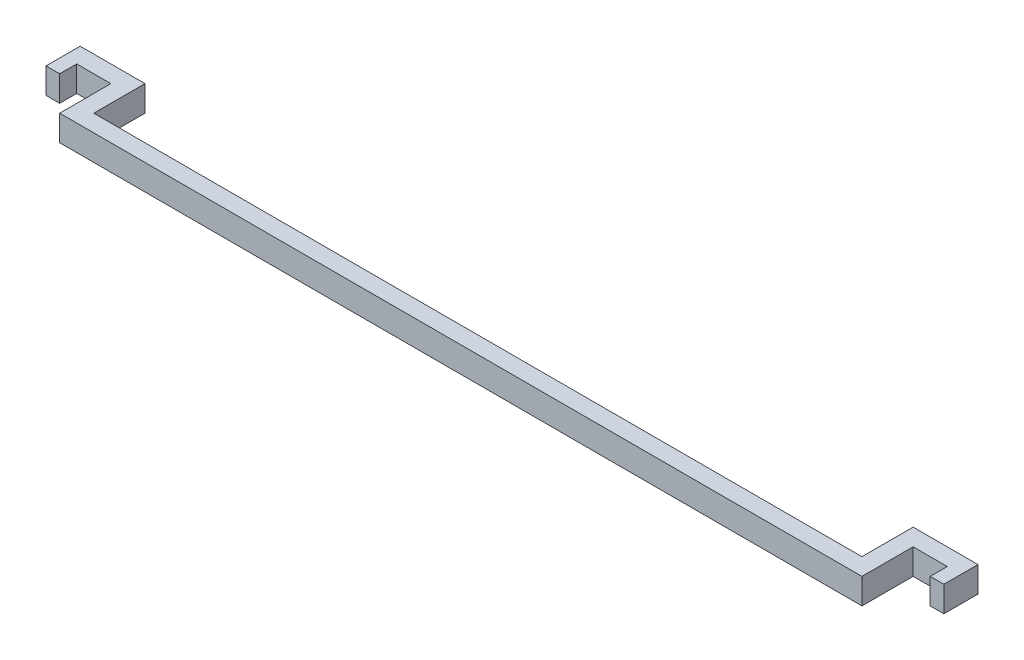
SolidWorks part; units mm, degrees
ref_plane "前视基准面" through (0, 0, 0) normal (0, 0, 1) x (1, 0, 0)
ref_plane "上视基准面" through (0, 0, 0) normal (0, 1, 0) x (1, 0, 0)
ref_plane "右视基准面" through (0, 0, 0) normal (1, 0, 0) x (0, 0, -1)
sketch "草图1" plane through (0, 0, 0) normal (0, 0, 1) x (1, 0, 0)
  line L1 (0, 0) -> (510, 0)
  line L2 (0, 0) -> (0, 15)
  line L3 (0, 15) -> (510, 15)
  line L4 (510, 0) -> (510, 15)
  dimension "D1" = 510
  dimension "D2" = 15
extrude "凸台-拉伸1" add sketch "草图1" along normal blind 10
sketch "草图2" plane through (0, 0, 10) normal (0, 0, 1) x (1, 0, 0)
  line L1 (510, 15) -> (518, 15)
  line L2 (510, 15) -> (510, 0)
  line L3 (510, 0) -> (518, 0)
  line L4 (518, 15) -> (518, 0)
  line L5 (0, 15) -> (-8, 15)
  line L6 (0, 15) -> (0, 0)
  line L7 (0, 0) -> (-8, 0)
  line L8 (-8, 15) -> (-8, 0)
  dimension "D1" = 8
  dimension "D2" = 8
extrude "凸台-拉伸2" add sketch "草图2" along normal blind 10 and the other way blind 10
sketch "草图3" plane through (0, 0, 0) normal (0, -1, 0) x (1, 0, 0)
  line L0 (0, 10) -> (510, 10) construction
  line L1 (20, 10) -> (30, 10)
  line L4 (30, 10) -> (30, 30)
  line L7 (30, 30) -> (480, 30)
  line L11 (490, 10) -> (480, 10)
  line L12 (480, 30) -> (480, 10)
  line L14 (490, 40) -> (490, 10)
  line L15 (510, 10) -> (510, 20) construction
  line L16 (0, 10) -> (0, 20) construction
  line L17 (490, 40) -> (20, 40)
  line L18 (20, 40) -> (20, 10)
  line M17 (510, 10) -> (0, 10)
  dimension "D1" = 10
  dimension "D2" = 10
  dimension "D3" = 20
  dimension "D4" = 10
  dimension "D5" = 20
  dimension "D6" = 30
extrude "凸台-拉伸3" add sketch "草图3" against normal up to surface (15 mm away) contours L7 L12 L4 M17 region at (255, 0, 33.8235) up to face at (255, 15, 12.5)
sketch "草图4" plane through (0, 0, 0) normal (0, -1, 0) x (1, 0, 0)
  line L0 (-8, 0) -> (518, 0) construction
  line L1 (30, 10) -> (480, 10)
  line L2 (30, 10) -> (30, 0)
  line L3 (30, 0) -> (480, 0)
  line L4 (480, 10) -> (480, 0)
  line L5 (480, 30) -> (480, 10) construction
extrude "切除-拉伸1" cut sketch "草图4" against normal through all
